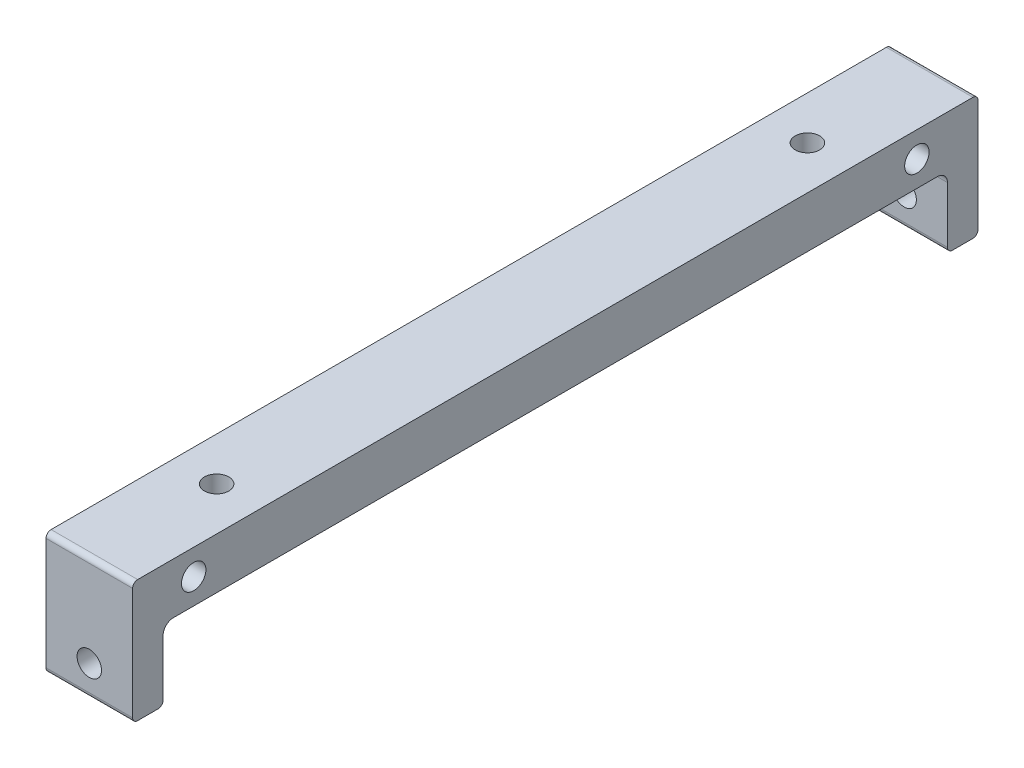
SolidWorks part; units mm, degrees
material "6061 Alloy"
ref_plane "Frontal" through (0, 0, 0) normal (0, 0, 1) x (1, 0, 0)
ref_plane "Superior" through (0, 0, 0) normal (0, 1, 0) x (1, 0, 0)
ref_plane "Direito" through (0, 0, 0) normal (1, 0, 0) x (0, 0, -1)
sketch "Sketch1" plane through (0, 0, 0) normal (0, 0, 1) x (1, 0, 0)
  line L1 (-4.25, -6) -> (4.25, -6)
  line L2 (-4.25, -6) -> (-4.25, 6)
  line L3 (-4.25, 6) -> (4.25, 6)
  line L4 (4.25, -6) -> (4.25, 6)
  line L5 (-4.25, -6) -> (4.25, 6) construction
  line L6 (-4.25, 6) -> (4.25, -6) construction
  point P0 (0, 0)
  dimension "D1" = 8.5
  dimension "D2" = 12
extrude "Boss-Extrude1" add sketch "Sketch1" along normal mid plane 83
sketch "Sketch2" plane through (4.25, 0, 0) normal (1, 0, 0) x (0, 0, -1)
  line L0 (-37.5, 1) -> (37.5, 1)
  line L1 (38.5, 0) -> (38.5, -6)
  line L2 (-41.5, -6) -> (41.5, -6) construction
  line L3 (38.5, -6) -> (-38.5, -6)
  line L4 (-38.5, -6) -> (-38.5, 0)
  line L5 (-41.5, 6) -> (41.5, 6) construction
  line L6 (-41.5, -6) -> (-41.5, 6) construction
  line L7 (41.5, -6) -> (41.5, 6) construction
  arc A0 (-37.5, 1) -> (-38.5, 0) centre (-37.5, 0) ccw
  arc A1 (37.5, 1) -> (38.5, 0) centre (37.5, 0) cw
  dimension "D4" = 1
  dimension "D5" = 1
  dimension "D1" = 5
  dimension "D2" = 3
  dimension "D3" = 3
extrude "Cut-Extrude1" cut sketch "Sketch2" against normal through all
fillet "Fillet1" radius 0.5 6 edges at (0, 6, -41.5) (0, 6, 41.5) (0, -6, -41.5) (0, -6, -38.5) (0, -6, 38.5) (0, -6, 41.5)
hole_wizard "M2 Hole1-J" positions "Sketch10" profile "Sketch9" hole size "M2" standard "DIN"
sketch "Sketch10" plane through (4.25, 0, 0) normal (1, 0, 0) x (0, 0, -1)
  line L0 (-41, 6) -> (41, 6) construction
  line L1 (-41.5, -5.5) -> (-41.5, 5.5) construction
  line L2 (41.5, -5.5) -> (41.5, 5.5) construction
  point P0 (-35.5, 3.5)
  point P2 (35.5, 3.5)
  dimension "D1" = 2.5
  dimension "D2" = 6
  dimension "D3" = 6
sketch "Sketch9" plane through (4.25, 3.5, 35.5) normal (0, 1, 0) x (0, 0, -1)
  line L0 (0, 0) -> (0, 5.721)
  line L1 (0, 5.721) -> (1.2, 5)
  line L2 (1.2, 5) -> (1.2, 0)
  line L5 (1.2, 0) -> (0, 0)
  line L10 (0, 5.721) -> (-1.2, 5) construction
  line L11 (0, -6.35) -> (0, 107.95) construction
  dimension "Hole Dia." = 2.4
  dimension "Hole Depth" = 5
  dimension "Drill Angle" = 118
hole_wizard "M2 Hole2-K" positions "Sketch19" profile "Sketch18" hole size "M2" standard "DIN"
sketch "Sketch19" plane through (-4.25, 0, 0) normal (-1, 0, 0) x (0, 0, 1)
  line L0 (-41.5, 5.5) -> (-41.5, -5.5) construction
  line L1 (41.5, 5.5) -> (41.5, -5.5) construction
  line L2 (41, 6) -> (-41, 6) construction
  point P0 (-21.5, 3.5)
  point P2 (21.5, 3.5)
  dimension "D1" = 20
  dimension "D2" = 20
  dimension "D3" = 2.5
sketch "Sketch18" plane through (-4.25, 3.5, -21.5) normal (0, 1, 0) x (0, 0, 1)
  line L0 (0, 0) -> (0, 5.721)
  line L1 (0, 5.721) -> (1.2, 5)
  line L2 (1.2, 5) -> (1.2, 0)
  line L5 (1.2, 0) -> (0, 0)
  line L10 (0, 5.721) -> (-1.2, 5) construction
  line L11 (0, -6.35) -> (0, 107.95) construction
  dimension "Hole Dia." = 2.4
  dimension "Hole Depth" = 5
  dimension "Drill Angle" = 118
hole_wizard "M2 Hole3-L" positions "Sketch8" profile "Sketch7" hole size "M2" standard "DIN"
sketch "Sketch8" plane through (0, 0, 41.5) normal (0, 0, 1) x (1, 0, 0)
  line L0 (4.25, -6) -> (-4.25, -6) construction
  point P0 (0, -3)
  dimension "D1" = 3
sketch "Sketch7" plane through (0, -3, 41.5) normal (1, 0, 0) x (0, -1, 0)
  line L0 (0, 0) -> (0, 10.721)
  line L1 (0, 10.721) -> (1.2, 10)
  line L2 (1.2, 10) -> (1.2, 0)
  line L5 (1.2, 0) -> (0, 0)
  line L10 (0, 10.721) -> (-1.2, 10) construction
  line L11 (0, -6.35) -> (0, 107.95) construction
  dimension "Hole Dia." = 2.4
  dimension "Hole Depth" = 10
  dimension "Drill Angle" = 118
hole_wizard "M2 Hole4-M" positions "Sketch15" profile "Sketch14" hole size "M2" standard "DIN" end condition through all
sketch "Sketch15" plane through (0, 6, 0) normal (0, 1, 0) x (1, 0, 0)
  line L0 (-4.25, -41) -> (-4.25, 41) construction
  line L1 (-4.25, 41.5) -> (4.25, 41.5) construction
  line L2 (4.25, -41.5) -> (-4.25, -41.5) construction
  point P0 (0, 29)
  point P2 (0, -29)
  dimension "D1" = 4.25
  dimension "D2" = 12.5
  dimension "D3" = 12.5
sketch "Sketch14" plane through (0, 6, -29) normal (1, 0, 0) x (0, 0, 1)
  line L0 (0, 0) -> (0, 12)
  line L1 (0, 12) -> (1.2, 12)
  line L2 (1.2, 12) -> (1.2, 0)
  line L5 (1.2, 0) -> (0, 0)
  line L11 (0, -6.35) -> (0, 107.95) construction
  dimension "Thru Hole Dia." = 2.4
  dimension "Thru Hole Depth" = 12
hole_wizard "M2 Hole5-N" positions "Sketch12" profile "Sketch11" hole size "M2" standard "DIN"
sketch "Sketch12" plane through (-4.25, 0, 0) normal (-1, 0, 0) x (0, 0, 1)
  line L0 (41, 6) -> (-41, 6) construction
  point P0 (0, 3.5)
  dimension "D1" = 2.5
sketch "Sketch11" plane through (-4.25, 3.5, 0) normal (0, 1, 0) x (0, 0, 1)
  line L0 (0, 0) -> (0, 4.721)
  line L1 (0, 4.721) -> (1.2, 4)
  line L2 (1.2, 4) -> (1.2, 0)
  line L5 (1.2, 0) -> (0, 0)
  line L10 (0, 4.721) -> (-1.2, 4) construction
  line L11 (0, -6.35) -> (0, 107.95) construction
  dimension "Hole Dia." = 2.4
  dimension "Hole Depth" = 4
  dimension "Drill Angle" = 118
hole_wizard "M2 Hole6-P" positions "Sketch17" profile "Sketch16" hole size "M2" standard "DIN"
sketch "Sketch17" plane through (0, 0, -41.5) normal (0, 0, -1) x (-1, 0, 0)
  line L0 (4.25, 5.5) -> (4.25, -5.5) construction
  line L1 (-4.25, 6) -> (4.25, 6) construction
  point P0 (0, -3)
  dimension "D1" = 4.25
  dimension "D2" = 9
sketch "Sketch16" plane through (0, -3, -41.5) normal (1, 0, 0) x (0, 1, 0)
  line L0 (0, 0) -> (0, 10.721)
  line L1 (0, 10.721) -> (1.2, 10)
  line L2 (1.2, 10) -> (1.2, 0)
  line L5 (1.2, 0) -> (0, 0)
  line L10 (0, 10.721) -> (-1.2, 10) construction
  line L11 (0, -6.35) -> (0, 107.95) construction
  dimension "Hole Dia." = 2.4
  dimension "Hole Depth" = 10
  dimension "Drill Angle" = 118
